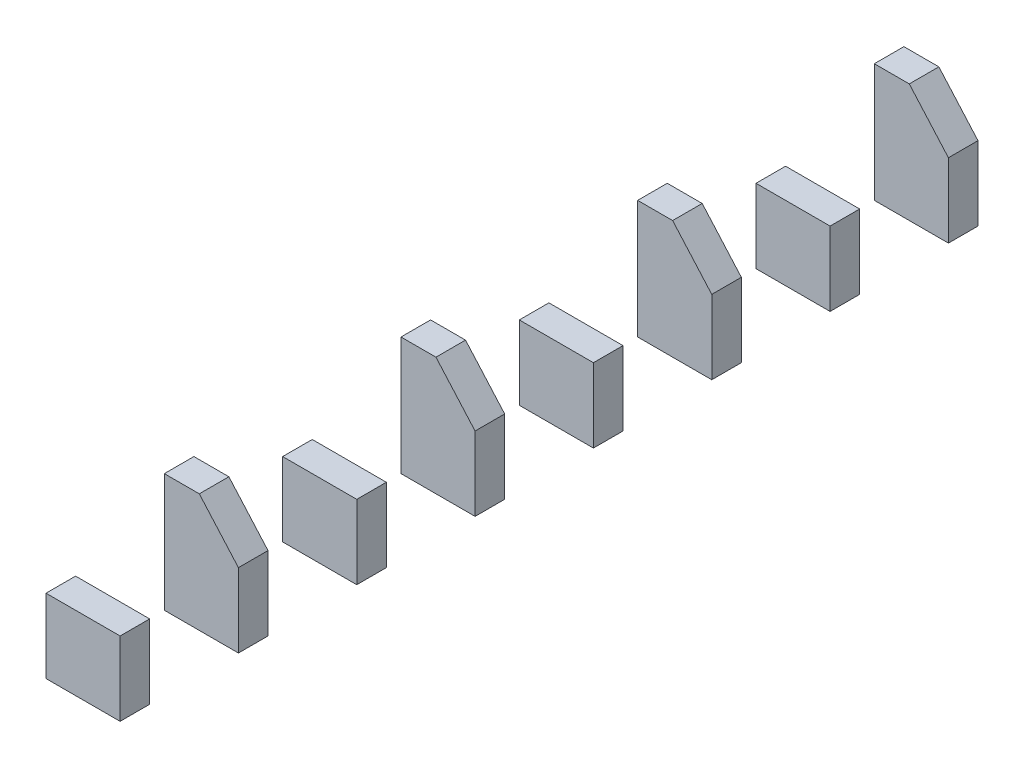
SolidWorks part; units mm, degrees
ref_plane "Front Plane" through (0, 0, 0) normal (0, 0, 1) x (1, 0, 0)
ref_plane "Top Plane" through (0, 0, 0) normal (0, 1, 0) x (1, 0, 0)
ref_plane "Right Plane" through (0, 0, 0) normal (1, 0, 0) x (0, 0, -1)
sketch "Sketch1" plane through (0, 0, 0) normal (0, 0, 1) x (1, 0, 0)
  line L0 (0, 0) -> (0, 101.6)
  line L1 (0, 101.6) -> (30.0202, 101.6)
  line L2 (30.0202, 101.6) -> (63.6212, 63.5)
  line L3 (63.6212, 63.5) -> (63.6212, 0)
  line L4 (63.6212, 0) -> (0, 0)
  dimension "D1" = 50.8
  dimension "D2" = 63.5
  dimension "D3" = 63.6212
  dimension "D4" = 101.6
extrude "Boss-Extrude1" add sketch "Sketch1" along normal blind 25.4
ref_plane "Plane1" through (0, 0, 101.6) normal (0, 0, 1) x (1, 0, 0)
sketch "Sketch2" plane through (0, 0, 101.6) normal (0, 0, 1) x (1, 0, 0)
  line L0 (0, 0) -> (0, 63.5)
  line L1 (0, 101.6) -> (0, 0) construction
  line L2 (0, 63.5) -> (63.6212, 63.5)
  line L3 (63.6212, 63.5) -> (63.6212, 0)
  line L4 (63.6212, 0) -> (0, 0)
  dimension "D1" = 63.5
extrude "Boss-Extrude2" add sketch "Sketch2" along normal blind 25.4 separate body
sketch "Sketch3" plane through (0, 0, 0) normal (0, -1, 0) x (1, 0, 0)
  line L0 (0, 0) -> (0, 88.9) construction
ref_axis "Axis2" through (0, 0, 0) along (0, 0, 1)
pattern_linear "LPattern1" count 4 spacing 203.2 along (0, 0, 1) of "Boss-Extrude1"
pattern_linear "LPattern2" count 4 spacing 203.2 along (0, 0, 1) of "Boss-Extrude2"
